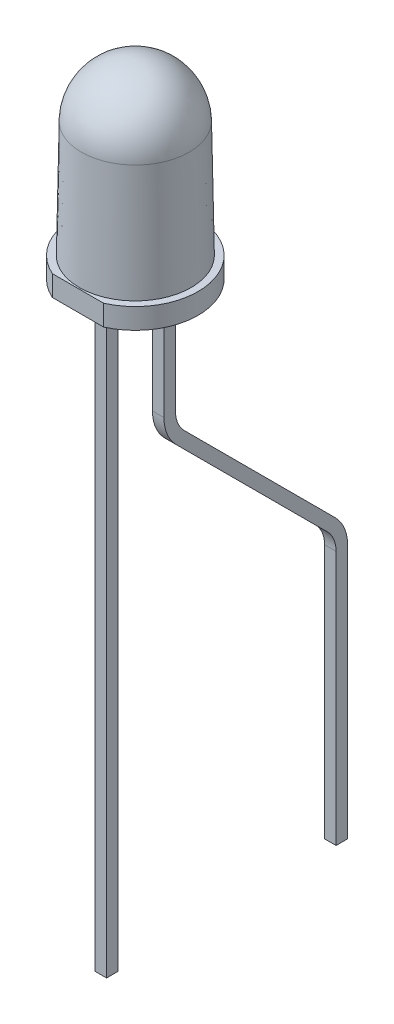
SolidWorks part; units mm, degrees
ref_plane "Front Plane" through (0, 0, 0) normal (0, 0, 1) x (1, 0, 0)
ref_plane "Top Plane" through (0, 0, 0) normal (0, 1, 0) x (1, 0, 0)
ref_plane "Right Plane" through (0, 0, 0) normal (1, 0, 0) x (0, 0, -1)
sketch "Sketch1" plane through (0, 0, 0) normal (1, 0, 0) x (0, 0, -1)
  line L0 (0, 8.4074) -> (0, 0)
  line L1 (0, 0) -> (2.7813, 0)
  line L2 (2.4765, 0.9144) -> (2.3876, 6.0607)
  line L3 (2.4765, 0.9144) -> (2.7813, 0.9144)
  line L4 (2.7813, 0.9144) -> (2.7813, 0)
  arc A0 (2.3876, 6.0607) -> (0, 8.4074) centre (0, 6.0194) ccw
  dimension "D1" = 2.4765
  dimension "D2" = 2.3876
  dimension "D3" = 7.493
  dimension "D4" = 2.7813
  dimension "D5" = 0.9144
revolve "Revolve1" add sketch "Sketch1" angle 360 about L0
ref_plane "Plane1" through (0, 0, 2.54) normal (0, 0, 1) x (1, 0, 0)
sketch "Sketch2" plane through (0, 0, 2.54) normal (0, 0, 1) x (1, 0, 0)
  line L1 (-4.7358, 11.252) -> (3.4904, 11.252)
  line L2 (-4.7358, 11.252) -> (-4.7358, -1.5294)
  line L3 (-4.7358, -1.5294) -> (3.4904, -1.5294)
  line L4 (3.4904, 11.252) -> (3.4904, -1.5294)
extrude "Extrude1" cut sketch "Sketch2" along normal through all
sketch "Sketch3" plane through (0, 0, 0) normal (1, 0, 0) x (0, 0, -1)
  line L0 (-1.27, 0) -> (-1.27, -25.908)
  line L1 (-2.54, 0) -> (2.7813, 0) construction
  dimension "D1" = 1.27
  dimension "D2" = 25.908
sketch "Sketch5" plane through (0, 0, 0) normal (1, 0, 0) x (0, 0, -1)
  line L0 (1.27, 0) -> (1.27, -5.6924)
  line L1 (-2.54, 0) -> (2.7813, 0) construction
  line L2 (1.735, -6.815) -> (8.425, -13.505)
  line L3 (8.89, -14.6276) -> (8.89, -25.908)
  line L4 (-1.27, 0) -> (-1.27, -25.908) construction
  arc A0 (1.27, -5.6924) -> (1.735, -6.815) centre (2.8575, -5.6924) ccw
  arc A1 (8.425, -13.505) -> (8.89, -14.6276) centre (7.3025, -14.6276) cw
  point P12 (1.27, -6.35)
  dimension "D5" = 1.5875
  dimension "D1" = 6.35
  dimension "D2" = 45
  dimension "D3" = 1.27
  dimension "D4" = 10.16
sketch "Sketch6" plane through (0, 0, 0) normal (0, 1, 0) x (1, 0, 0)
  line L0 (-0.254, -1.524) -> (0.254, -1.016) construction
  line L1 (0.254, -1.524) -> (-0.254, -1.524)
  line L2 (0.254, -1.524) -> (0.254, -1.016)
  line L3 (0.254, -1.016) -> (-0.254, -1.016)
  line L4 (-0.254, -1.524) -> (-0.254, -1.016)
  dimension "D1" = 0.508
  dimension "D2" = 0.508
extrude "Extrude2" add sketch "Sketch6" against normal up to vertex up to point (0, -25.908, 1.27)
sketch "Sketch7" plane through (0, 0, 0) normal (0, 1, 0) x (1, 0, 0)
  line L0 (-0.254, 1.016) -> (0.254, 1.524) construction
  line L1 (0.254, 1.016) -> (-0.254, 1.016)
  line L2 (0.254, 1.016) -> (0.254, 1.524)
  line L3 (0.254, 1.524) -> (-0.254, 1.524)
  line L4 (-0.254, 1.016) -> (-0.254, 1.524)
  dimension "D1" = 0.508
  dimension "D2" = 0.508
sweep "Sweep1" add profiles "Sketch7" path "Sketch5"
ref_axis "Centerline" [suppressed] through (0, -14.2433, 0) along (0, 1, 0)
